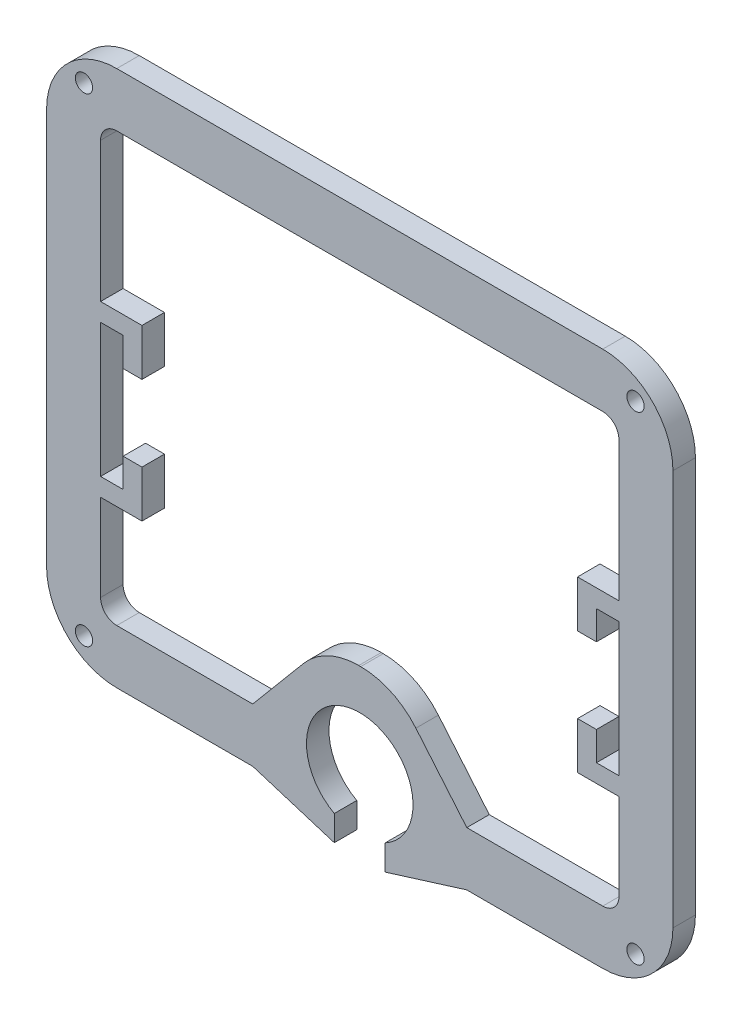
SolidWorks part; units mm, degrees
material "Delrin 2700 NC010, Low Viscosity Acetal Copolymer (SS)"
ref_plane "Front Plane" through (0, 0, 0) normal (0, 0, 1) x (1, 0, 0)
ref_plane "Top Plane" through (0, 0, 0) normal (0, 1, 0) x (1, 0, 0)
ref_plane "Right Plane" through (0, 0, 0) normal (1, 0, 0) x (0, 0, -1)
sketch "Sketch1" plane through (0, 0, 0) normal (0, 0, 1) x (1, 0, 0)
  line L0 (-17.145, -18.923) -> (-7.5425, -18.923)
  line L1 (-18.288, 13.97) -> (-18.288, -13.97)
  line L2 (-17.145, -15.113) -> (-7.5521, -15.113)
  line L3 (7.5521, -15.113) -> (17.145, -15.113)
  line L4 (18.288, 13.97) -> (18.288, -13.97)
  line L5 (-1000, 0) -> (49000, 0) construction
  line L6 (-1.7968, -18.923) -> (-1.7968, -20.7107)
  line L7 (7.5425, -18.923) -> (17.145, -18.923)
  line L8 (17.145, 15.113) -> (-17.145, 15.113)
  line L9 (-7.5521, -15.113) -> (-3.9596, -10.8316)
  line L10 (-22.098, 13.97) -> (-22.098, -13.97)
  line L11 (7.5521, -15.113) -> (3.9596, -10.8316)
  line L12 (-0.0681, -9.017) -> (0.0681, -9.017)
  line L13 (22.098, 13.97) -> (22.098, -13.97)
  line L14 (17.145, 18.923) -> (-17.145, 18.923)
  line L15 (1.7968, -18.923) -> (1.7968, -20.7107)
  line L16 (-7.5425, -18.923) -> (-1.7968, -20.7107)
  line L17 (7.5425, -18.923) -> (1.7968, -20.7107)
  line L18 (0, 12.5532) -> (0, -24.2768) construction
  line L19 (1.7968, -18.923) -> (17.145, -18.923) construction
  line L20 (-17.145, -18.923) -> (-1.7968, -18.923) construction
  arc A0 (1.7968, -18.923) -> (-1.7968, -18.923) centre (0, -15.621) ccw
  arc A1 (-17.145, -15.113) -> (-18.288, -13.97) centre (-17.145, -13.97) cw
  arc A2 (-0.0681, -9.017) -> (-3.9596, -10.8316) centre (-0.0681, -14.097) ccw
  arc A3 (18.288, -13.97) -> (17.145, -15.113) centre (17.145, -13.97) cw
  arc A4 (17.145, 15.113) -> (18.288, 13.97) centre (17.145, 13.97) cw
  arc A5 (-17.145, -18.923) -> (-22.098, -13.97) centre (-17.145, -13.97) cw
  arc A6 (22.098, -13.97) -> (17.145, -18.923) centre (17.145, -13.97) cw
  arc A7 (17.145, 18.923) -> (22.098, 13.97) centre (17.145, 13.97) cw
  arc A8 (-17.145, 18.923) -> (-22.098, 13.97) centre (-17.145, 13.97) ccw
  circle A9 centre (-19.4575, 16.891) radius 0.6096
  circle A10 centre (19.4575, 16.891) radius 0.6096
  arc A11 (-17.145, 15.113) -> (-18.288, 13.97) centre (-17.145, 13.97) ccw
  arc A12 (0.0681, -9.017) -> (3.9596, -10.8316) centre (0.0681, -14.097) cw
  circle A13 centre (19.4575, -16.891) radius 0.6096
  circle A14 centre (-19.4575, -16.891) radius 0.6096
  circle A15 centre (0, -15.621) radius 5.3975 construction
  arc A18 (7.5521, -15.113) -> (-7.5521, -15.113) centre (0, -15.621) ccw construction
  point P0 (0, 0)
  dimension "D4" = 3.302
  dimension "D6" = 37.846
  dimension "D7" = 44.196
  dimension "D8" = 3.81
  dimension "D9" = 6.604
  dimension "D5" = 1.2192
  dimension "D2" = 4.953
  dimension "D3" = 7.5184
  dimension "D10" = 5.08
  dimension "D11" = 5.08
  dimension "D14" = 10.795
  dimension "D12" = 16.891
  dimension "D13" = 19.4575
extrude "Boss-Extrude1" add sketch "Sketch1" along normal blind 1.5875
sketch "Sketch2" plane through (-18.288, 0, 0) normal (1, 0, 0) x (0, 0, -1)
  line L0 (0, 2.8448) -> (-1.5875, 2.8448)
  line L1 (0, -6.574) -> (-1.5875, -6.574) construction
  line L2 (-1.5875, -15.113) -> (0, -15.113)
  line L3 (-1.5875, -15.113) -> (0, -15.113) construction
  line L4 (0, -13.97) -> (0, 13.97)
  line L5 (0, 13.97) -> (-1.5875, 13.97)
  line L6 (-1.5875, 13.97) -> (-1.5875, -13.97)
  line L7 (0, 13.97) -> (-1.5875, 13.97)
  line L8 (0, -13.97) -> (0, 4.1148)
  line L9 (-1.5875, -15.113) -> (-1.5875, -7.844)
  line L10 (-1.5875, 4.1148) -> (-1.5875, -13.97)
  line L11 (-1.5875, -13.97) -> (0, -13.97)
  line L12 (0, -15.113) -> (0, -7.844)
  line L13 (0, 4.1148) -> (-1.5875, 4.1148)
  line L14 (-1.5875, 2.8448) -> (-1.5875, -6.6447)
  line L15 (-1.5875, 4.1148) -> (-1.5875, 2.8448)
  line L16 (0, 2.8448) -> (0, 4.1148)
  line L17 (0, -7.9147) -> (0, 1.4693)
  line L18 (-1.5875, -7.9147) -> (-1.5875, -6.6447)
  line L19 (0, -6.574) -> (-1.5875, -6.574)
  line L21 (0, -7.844) -> (-1.5875, -7.844)
  line L22 (0, -7.844) -> (0, -13.97)
  line L23 (-1.5875, -7.844) -> (-1.5875, -13.97)
  line L24 (47.9467, 2.8448) -> (-14.2384, 2.8448) construction
  line L28 (-1.5875, -13.97) -> (0, -13.97)
  line L29 (47.5364, -9.6894) -> (-14.2384, -5.6408) construction
  line M5 (0, -13.97) -> (0, 13.97)
  line M7 (-1.5875, 13.97) -> (-1.5875, -13.97)
  dimension "D1" = 0
  dimension "D2" = 1.27
  dimension "D4" = 1.27
extrude "Boss-Extrude2" add sketch "Sketch2" along normal blind 2.921 contours L13 L10 L0 M5 | L19 L17 L8 L0 L10 M7 | L21 L8 L19 L18 M5 M7 region at (-18.288, -1.8646, 0.7937) region at (-18.288, 3.4798, 0.7937) region at (-18.288, -7.209, 0.7937)
extrude "Cut-Extrude1" cut sketch "Sketch2<3>" along normal blind 1.5875 contours L19 L8 L10 | L19 L17 L0 M5 M7 region at (-18.288, -1.8646, 0.7937)
sketch "Sketch2<3>" plane through (-18.288, 0, 0) normal (1, 0, 0) x (0, 0, -1) same geometry as "Sketch2"
sketch "Sketch3" plane through (-16.7005, 0, 0) normal (-1, 0, 0) x (0, 0, 1)
  line L0 (0, 2.8448) -> (1.5875, 2.8448) construction
  line L1 (0, -6.574) -> (1.5875, -6.574) construction
  line L2 (0, 2.8448) -> (1.5875, 2.8448)
  line L3 (0, -6.574) -> (1.5875, -6.574)
  line L4 (0, 0.8128) -> (1.5875, 0.8128)
  line L5 (0, -4.542) -> (1.5875, -4.542)
  line L6 (1.5875, 0.8128) -> (1.5875, -4.542)
  line L7 (0, -4.542) -> (0, 0.8128)
  line M2 (1.5875, -6.574) -> (1.5875, 2.8448)
  line M4 (0, 2.8448) -> (0, -6.574)
  dimension "D1" = 2.032
  dimension "D2" = 2.032
extrude "Cut-Extrude2" cut sketch "Sketch3" against normal up to surface (1.3335 mm away) contours L5 L4 M4 M2 region at (-16.7005, -1.8646, 0.7937) up to face at (-15.367, -1.8646, 0.7937)
mirror "Mirror1" about plane through (0, 0, 0) normal (1, 0, 0) of "Cut-Extrude2", "Boss-Extrude2", "Cut-Extrude1"
